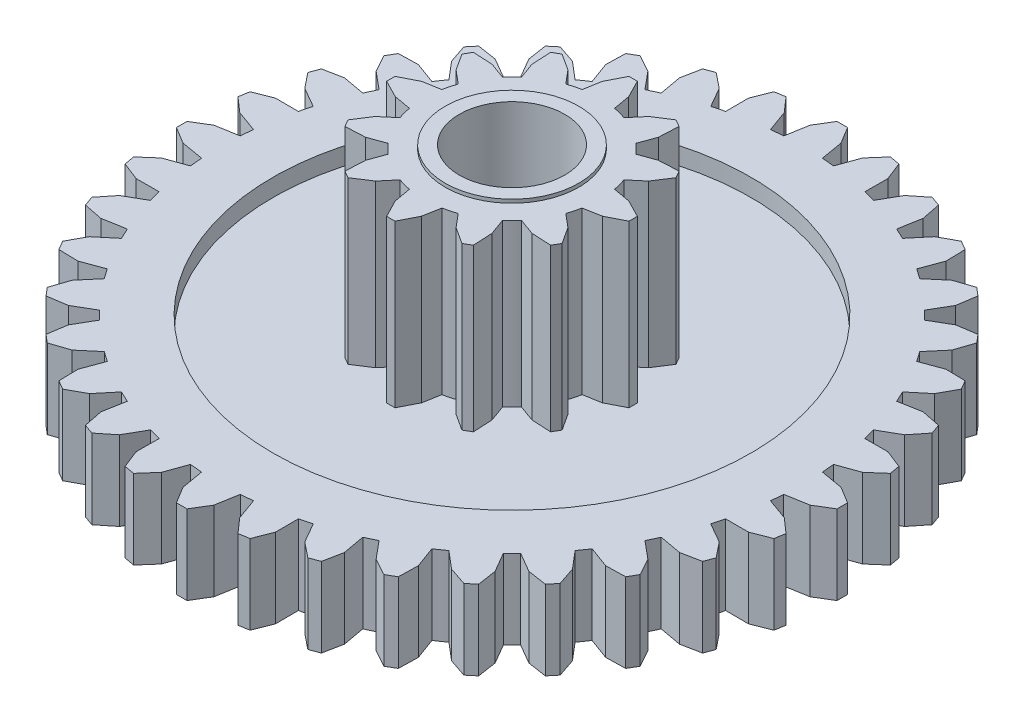
SolidWorks part; units mm, degrees
ref_plane "Front Plane" through (0, 0, 0) normal (0, 0, 1) x (1, 0, 0)
ref_plane "Top Plane" through (0, 0, 0) normal (0, 1, 0) x (1, 0, 0)
ref_plane "Right Plane" through (0, 0, 0) normal (1, 0, 0) x (0, 0, -1)
sketch "Sketch1" plane through (0, 0, 0) normal (0, 1, 0) x (1, 0, 0)
  circle A0 centre (0, 0) radius 8.3
  dimension "D1" = 16.6
extrude "Boss-Extrude1" add sketch "Sketch1" along normal mid plane 1.26
sketch "Sketch4" plane through (0, 0, 0) normal (0, 1, 0) x (1, 0, 0)
  circle A0 centre (0, 0) radius 6.8
  circle A1 centre (0, 0) radius 8.3
  circle A2 centre (0, 0) radius 8.3 construction
  dimension "D1" = 1.5
extrude "Boss-Extrude2" add sketch "Sketch4" along normal mid plane 2.26
ref_axis "Axis1" through (0, 7.12, 0) along (0, -1, 0)
sketch "Sketch6" plane through (0, 0.63, 0) normal (0, 1, 0) x (1, 0, 0)
  circle A0 centre (0, 0) radius 2.5
  dimension "D1" = 5
extrude "Boss-Extrude4" add sketch "Sketch6" along normal blind 4.6
sketch "Sketch7" plane through (0, 0.63, 0) normal (0, 1, 0) x (1, 0, 0)
  line L2 (-0.4622, 2.4569) -> (0.4622, 2.4569)
  line L3 (0.4622, 2.4569) -> (0.375, 2.9469)
  line L4 (0.375, 2.9469) -> (0.1192, 3.4479)
  line L5 (-0.4622, 2.4569) -> (-0.375, 2.9469)
  line L7 (-0.375, 2.9469) -> (-0.1192, 3.4479)
  line L8 (-0.1192, 3.4479) -> (0.1192, 3.4479)
  circle A0 centre (0, 0) radius 3.45 construction
  circle A2 centre (0, 0) radius 2.5 construction
  point P5 (0, 3.4479)
  point P7 (0, 2.4569)
  dimension "D1" = 6.9
  dimension "D2" = 0.75
  dimension "D3" = 0.49
extrude "Boss-Extrude5" add sketch "Sketch7" along normal up to surface (4.6 mm away) up to face at (0, 5.23, 2.5)
pattern_circular "CirPattern2" count 12 every 30 about axis through (0, 7.12, 0) along (0, -1, 0) of "Boss-Extrude5"
sketch "Sketch8" plane through (0, 5.23, 0) normal (0, 1, 0) x (1, 0, 0)
  circle A0 centre (0, 0) radius 1.5
  circle A1 centre (0, 0) radius 1.9
  dimension "D1" = 3
  dimension "D2" = 3.8
extrude "Boss-Extrude6" add sketch "Sketch8" along normal blind 0.1
sketch "Sketch9" plane through (0, 5.23, 0) normal (0, 1, 0) x (1, 0, 0)
  circle A0 centre (0, 0) radius 1.5
  circle A1 centre (0, 0) radius 1.5 construction
extrude "Cut-Extrude1" cut sketch "Sketch9" against normal up to surface (5.86 mm away) up to face at (0, -0.63, 6.8)
sketch "Sketch10" plane through (0, -0.63, 0) normal (0, -1, 0) x (1, 0, 0)
  circle A0 centre (0, 0) radius 1.5
  circle A1 centre (0, 0) radius 2.5
  circle A2 centre (0, 0) radius 1.5 construction
  dimension "D1" = 5
extrude "Boss-Extrude7" add sketch "Sketch10" along normal blind 0.4
sketch "Sketch11" plane through (0, -1.13, 0) normal (0, -1, 0) x (1, 0, 0)
  line L0 (0.55, 8.2818) -> (0.44, 8.9218)
  line L1 (0.44, 8.9218) -> (0.15, 9.3988)
  line L2 (0.15, 9.3988) -> (-0.15, 9.3988)
  line L3 (-0.15, 9.3988) -> (-0.44, 8.9218)
  line L4 (-0.44, 8.9218) -> (-0.55, 8.2818)
  line L5 (-0.55, 8.2818) -> (0.55, 8.2818)
  circle A0 centre (0, 0) radius 8.3 construction
  circle A1 centre (0, 0) radius 9.4 construction
  point P9 (0, 9.3988)
  point P11 (0, 0)
  dimension "D1" = 18.8
  dimension "D2" = 0.3
  dimension "D3" = 1.1
  dimension "D4" = 0.88
  dimension "D5" = 0.64
extrude "Boss-Extrude8" add sketch "Sketch11" against normal up to surface (2.26 mm away) up to face at (0, 1.13, 8.3)
pattern_circular "CirPattern3" count 36 every 10 about axis through (0, 5.33, 0) along (0, -1, 0) of "Boss-Extrude8"
sketch "Sketch12" plane through (0, -1.13, 0) normal (0, -1, 0) x (1, 0, 0)
  circle A0 centre (0, 0) radius 6.8
  circle A1 centre (0, 0) radius 7.2
  circle A2 centre (0, 0) radius 6.8 construction
  dimension "D1" = 0.4
extrude "Boss-Extrude9" add sketch "Sketch12" along normal blind 0.2
